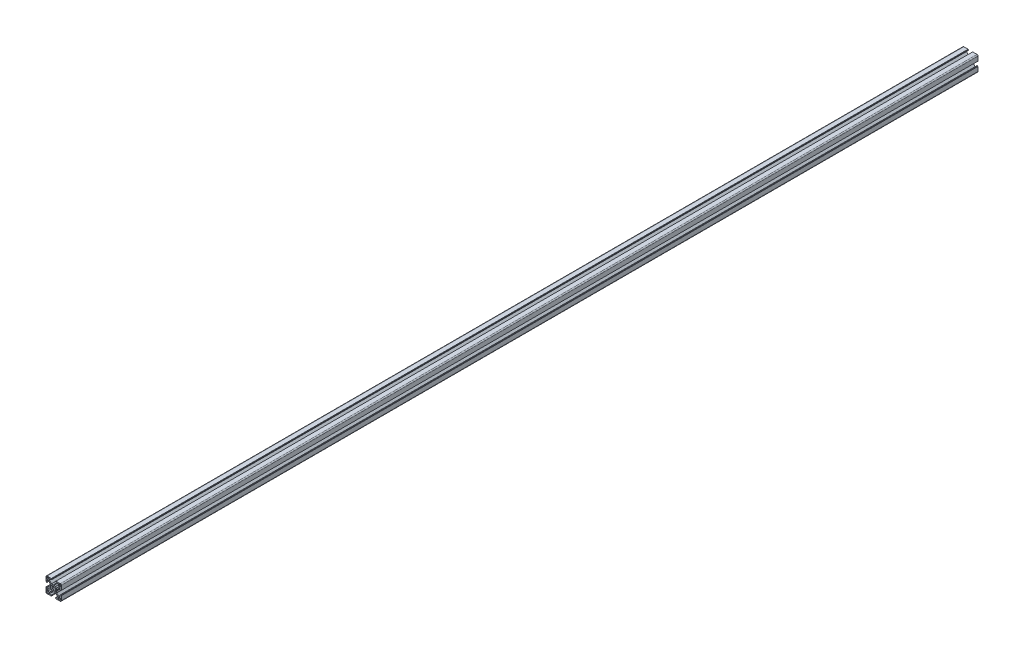
SolidWorks part; units mm, degrees
ref_plane "Front Plane" through (0, 0, 0) normal (0, 0, 1) x (1, 0, 0)
ref_plane "Top Plane" through (0, 0, 0) normal (0, 1, 0) x (1, 0, 0)
ref_plane "Right Plane" through (0, 0, 0) normal (1, 0, 0) x (0, 0, -1)
sketch "Sketch1" plane through (0, 0, 0) normal (0, 0, 1) x (1, 0, 0)
  line L0 (-15, 0) -> (15, 0) construction
  line L1 (0, -15) -> (0, 15) construction
  line L2 (-4.5, 15) -> (4.5, 15) construction
  line L3 (-4, -15) -> (4, -15) construction
  line L4 (-4.5, 15) -> (-4.5, 14.5)
  line L5 (-4.5, 14.5) -> (-4, 14.5)
  line L6 (-4, 14.5) -> (-4, 13.29)
  line L7 (-4.5, 12.79) -> (-7.7675, 12.79)
  line L8 (-8.2675, 12.29) -> (-8.2675, 10.2707)
  line L9 (-8.1211, 9.9171) -> (-4.3504, 6.1464)
  line L10 (-3.9968, 6) -> (0, 6)
  line L11 (0, 0) -> (-15, 15) construction
  line L12 (-4.5, 15) -> (-12.968, 15)
  line L14 (-12.705, 9.5135) -> (-10.5135, 9.5135)
  line L15 (-13.705, 10.5135) -> (-13.705, 12.705)
  line L16 (-12.705, 13.705) -> (-10.5135, 13.705)
  line L17 (-9.5135, 10.5135) -> (-9.5135, 12.705)
  line L18 (-13.705, 9.5135) -> (-9.5135, 13.705) construction
  line L19 (-13.705, 13.705) -> (-9.5135, 9.5135) construction
  line L20 (-3.1568, 4.5038) -> (-1.5303, 3.1477) construction
  line L21 (-4.5038, 3.1568) -> (-3.1477, 1.5303) construction
  line L22 (-6, 3.9968) -> (-6, 0)
  line L23 (-9.9171, 8.1211) -> (-6.1464, 4.3504)
  line L24 (-15, 4.5) -> (-15, 12.968)
  line L25 (-12.29, 8.2675) -> (-10.2707, 8.2675)
  line L26 (-12.79, 4.5) -> (-12.79, 7.7675)
  line L27 (-14.5, 4) -> (-13.29, 4)
  line L28 (-14.5, 4.5) -> (-14.5, 4)
  line L29 (-15, 4.5) -> (-14.5, 4.5)
  circle A0 centre (0, 0) radius 3.5
  arc A1 (-12.968, 15) -> (-15, 12.968) centre (-12.968, 12.968) ccw
  circle A2 centre (0, 0) radius 5.5 construction
  arc A3 (-10.5135, 9.5135) -> (-9.5135, 10.5135) centre (-10.5135, 10.5135) ccw
  arc A4 (-13.705, 12.705) -> (-12.705, 13.705) centre (-12.705, 12.705) cw
  arc A5 (-10.5135, 13.705) -> (-9.5135, 12.705) centre (-10.5135, 12.705) cw
  arc A6 (-12.705, 9.5135) -> (-13.705, 10.5135) centre (-12.705, 10.5135) cw
  arc A7 (-12.79, 4.5) -> (-13.29, 4) centre (-13.29, 4.5) cw
  arc A8 (-12.29, 8.2675) -> (-12.79, 7.7675) centre (-12.29, 7.7675) ccw
  arc A9 (-9.9171, 8.1211) -> (-10.2707, 8.2675) centre (-10.2707, 7.7675) ccw
  arc A10 (-6, 3.9968) -> (-6.1464, 4.3504) centre (-6.5, 3.9968) ccw
  arc A11 (-4.3504, 6.1464) -> (-3.9968, 6) centre (-3.9968, 6.5) ccw
  arc A12 (-4, 13.29) -> (-4.5, 12.79) centre (-4.5, 13.29) cw
  arc A13 (-7.7675, 12.79) -> (-8.2675, 12.29) centre (-7.7675, 12.29) ccw
  arc A14 (-8.2675, 10.2707) -> (-8.1211, 9.9171) centre (-7.7675, 10.2707) ccw
  point P4 (0, 0)
  point P8 (0, 0)
  point P13 (0, 15)
  point P15 (0, -15)
  point P16 (0, 6)
  point P23 (-11.6092, 11.6093)
  point P26 (0, 6)
  point P62 (-12.79, 4)
  point P65 (-12.79, 8.2675)
  point P68 (-10.0636, 8.2675)
  point P71 (-6, 4.2039)
  point P74 (-4.2039, 6)
  point P77 (-4, 12.79)
  point P80 (-8.2675, 12.79)
  point P83 (-8.2675, 10.0636)
  dimension "Center Hole Diameter" = 7
  dimension "D11" = 2.032
  dimension "D9" = 11
  dimension "D13" = 1
  dimension "D14" = 0.5
  dimension "Rail Height" = 30
  dimension "Rail Width" = 30
  dimension "T-Slot Width" = 8
  dimension "T-Slot Depth" = 9
  dimension "D1" = 9
  dimension "D2" = 45
  dimension "D3" = 8
  dimension "D4" = 2.21
  dimension "D5" = 16.535
  dimension "D7" = 2.54
  dimension "D6" = 1.295
  dimension "D8" = 1.246
  dimension "D10" = 10.36
  dimension "D12" = 1.905
sketch "Sketch2" plane through (0, 0, 0) normal (1, 0, 0) x (0, 0, -1)
  line L0 (-76.2, 0) -> (76.2, 0) construction
  line L2 (0, -15) -> (0, 15) construction
  line L3 (0, -15) -> (0, 15) construction
  line L4 (-76.2, -15) -> (-76.2, 15) construction
  line L5 (76.2, -15) -> (76.2, 15) construction
  point P0 (-38.7, 0)
  point P3 (0, 0)
  point P4 (38.7, 0)
  point P12 (-76.2, 0)
  point P14 (76.2, 0)
  dimension "Length" = 152.4
  dimension "D1" = 37.5
sketch "Sketch3" plane through (0, 0, 0) normal (0, 0, 1) x (1, 0, 0)
  line L0 (-4.5038, 3.1568) -> (-3.1477, 1.5303)
  line L1 (0, 3.5) -> (0, 5.5)
  line L2 (-5.5, 0) -> (-3.5, 0)
  line L7 (-6, 3.9968) -> (-6, 0) construction
  line L31 (-9.9171, 8.1211) -> (-6.1464, 4.3504) construction
  line L117 (-12.29, 8.2675) -> (-10.2707, 8.2675) construction
  line L118 (-12.79, 4.5) -> (-12.79, 7.7675) construction
  line L157 (-12.705, 9.5135) -> (-10.5135, 9.5135)
  line L158 (-9.5135, 10.5135) -> (-9.5135, 12.705)
  line L163 (-10.5135, 13.705) -> (-12.705, 13.705)
  line L164 (-13.705, 12.705) -> (-13.705, 10.5135)
  line L165 (-12.705, 9.5135) -> (-10.5135, 9.5135)
  line L166 (-9.5135, 10.5135) -> (-9.5135, 12.705)
  line L167 (-10.5135, 13.705) -> (-12.705, 13.705)
  line L168 (-13.705, 12.705) -> (-13.705, 10.5135)
  line L169 (-14.5, 4) -> (-13.29, 4) construction
  line L170 (-14.5, 4.5) -> (-14.5, 4) construction
  line L171 (-15, 4.5) -> (-14.5, 4.5) construction
  line L172 (-15, 4.5) -> (-15, 12.968) construction
  line L173 (-4.5, 15) -> (-12.968, 15) construction
  line L174 (-4.5, 15) -> (-4.5, 14.5) construction
  line L175 (-4.5, 14.5) -> (-4, 14.5) construction
  line L176 (-4, 14.5) -> (-4, 13.29) construction
  line L177 (-4.5, 12.79) -> (-7.7675, 12.79) construction
  line L178 (-8.2675, 12.29) -> (-8.2675, 10.2707) construction
  line L179 (-8.1211, 9.9171) -> (-4.3504, 6.1464) construction
  line L180 (-3.9968, 6) -> (0, 6) construction
  line L181 (-6, 3.9968) -> (-6, 0.866)
  line L182 (-9.9171, 8.1211) -> (-6.1464, 4.3504)
  line L183 (-12.29, 8.2675) -> (-10.2707, 8.2675)
  line L184 (-12.79, 4.5) -> (-12.79, 7.7675)
  line L185 (-14.5, 4) -> (-13.29, 4)
  line L186 (-14.5, 4.5) -> (-14.5, 4)
  line L187 (-15, 4.5) -> (-14.5, 4.5)
  line L188 (-15, 4.5) -> (-15, 12.968)
  line L189 (-4.5, 15) -> (-12.968, 15)
  line L190 (-4.5, 15) -> (-4.5, 14.5)
  line L191 (-4.5, 14.5) -> (-4, 14.5)
  line L192 (-4, 14.5) -> (-4, 13.29)
  line L193 (-4.5, 12.79) -> (-7.7675, 12.79)
  line L194 (-8.2675, 12.29) -> (-8.2675, 10.2707)
  line L195 (-8.1211, 9.9171) -> (-4.3504, 6.1464)
  line L196 (-3.9968, 6) -> (-0.866, 6)
  line L197 (-0.866, 6) -> (0, 5.5)
  line L198 (0, -15) -> (0, 15) construction
  line L199 (0, 0) -> (-15, 15) construction
  line L200 (0, 0) -> (-15, 15) construction
  line L201 (-3.1568, 4.5038) -> (-1.5303, 3.1477) construction
  line L202 (-3.1568, 4.5038) -> (-1.5303, 3.1477)
  line L203 (-6, 0.866) -> (-5.5, 0)
  line L204 (-15, 0) -> (15, 0) construction
  line L205 (-15, 0) -> (15, 0) construction
  line L206 (0, -15) -> (0, 15) construction
  arc A0 (-3.5, 0) -> (-3.1477, 1.5303) centre (0, 0) cw
  arc A10 (-6, 3.9968) -> (-6.1464, 4.3504) centre (-6.5, 3.9968) ccw construction
  circle A16 centre (0, 0) radius 3.5
  arc A18 (0, 3.5) -> (-1.5303, 3.1477) centre (0, 0) ccw
  arc A20 (-9.9171, 8.1211) -> (-10.2707, 8.2675) centre (-10.2707, 7.7675) ccw construction
  arc A22 (-12.29, 8.2675) -> (-12.79, 7.7675) centre (-12.29, 7.7675) ccw construction
  arc A28 (-13.29, 4) -> (-12.79, 4.5) centre (-13.29, 4.5) ccw construction
  arc A29 (-10.5135, 9.5135) -> (-9.5135, 10.5135) centre (-10.5135, 10.5135) ccw
  arc A30 (-9.5135, 12.705) -> (-10.5135, 13.705) centre (-10.5135, 12.705) ccw
  arc A31 (-12.705, 13.705) -> (-13.705, 12.705) centre (-12.705, 12.705) ccw
  arc A32 (-13.705, 10.5135) -> (-12.705, 9.5135) centre (-12.705, 10.5135) ccw
  arc A33 (-10.5135, 9.5135) -> (-9.5135, 10.5135) centre (-10.5135, 10.5135) ccw
  arc A34 (-9.5135, 12.705) -> (-10.5135, 13.705) centre (-10.5135, 12.705) ccw
  arc A35 (-12.705, 13.705) -> (-13.705, 12.705) centre (-12.705, 12.705) ccw
  arc A36 (-13.705, 10.5135) -> (-12.705, 9.5135) centre (-12.705, 10.5135) ccw
  arc A37 (-12.968, 15) -> (-15, 12.968) centre (-12.968, 12.968) ccw construction
  arc A38 (-4.5, 12.79) -> (-4, 13.29) centre (-4.5, 13.29) ccw construction
  arc A39 (-7.7675, 12.79) -> (-8.2675, 12.29) centre (-7.7675, 12.29) ccw construction
  arc A40 (-8.2675, 10.2707) -> (-8.1211, 9.9171) centre (-7.7675, 10.2707) ccw construction
  arc A41 (-4.3504, 6.1464) -> (-3.9968, 6) centre (-3.9968, 6.5) ccw construction
  arc A42 (-6, 3.9968) -> (-6.1464, 4.3504) centre (-6.5, 3.9968) ccw
  arc A43 (-9.9171, 8.1211) -> (-10.2707, 8.2675) centre (-10.2707, 7.7675) ccw
  arc A44 (-12.29, 8.2675) -> (-12.79, 7.7675) centre (-12.29, 7.7675) ccw
  arc A45 (-13.29, 4) -> (-12.79, 4.5) centre (-13.29, 4.5) ccw
  arc A46 (-12.968, 15) -> (-15, 12.968) centre (-12.968, 12.968) ccw
  arc A47 (-4.5, 12.79) -> (-4, 13.29) centre (-4.5, 13.29) ccw
  arc A48 (-7.7675, 12.79) -> (-8.2675, 12.29) centre (-7.7675, 12.29) ccw
  arc A49 (-8.2675, 10.2707) -> (-8.1211, 9.9171) centre (-7.7675, 10.2707) ccw
  arc A50 (-4.3504, 6.1464) -> (-3.9968, 6) centre (-3.9968, 6.5) ccw
  circle A51 centre (0, 0) radius 5.5 construction
  arc A52 (-3.1568, 4.5038) -> (-4.5038, 3.1568) centre (0, 0) ccw
  dimension "D3" = 60
  dimension "D4" = 60
  dimension "D1" = 0
  dimension "D2" = 0
extrude "Boss-Extrude1" add sketch "Sketch3" along normal mid plane 1800
pattern_circular "CirPattern1" count 4 over 360 about axis through (0, 0, 76.2) along (0, 0, -1) of "Boss-Extrude1"
ref_plane "Contact Plane1" through (15, 0, 0) normal (1, 0, 0) x (0, 0, -1)
ref_plane "Contact Plane2" through (0, -15, 0) normal (0, 1, 0) x (1, 0, 0)
ref_plane "Contact Plane3" through (-15, 0, 0) normal (1, 0, 0) x (0, 0, -1)
ref_plane "Contact Plane4" through (0, 15, 0) normal (0, 1, 0) x (1, 0, 0)
equation "\"D1@Sketch2\" = \"Rail Height@Sketch1\" * 1.25"
equation "\"D1@Sketch1\"=\"T-Slot Width@Sketch1\"+1mm"
equation "\"D3@Sketch1\"=\"T-Slot Width@Sketch1\""
equation "\"D1@Boss-Extrude1\"=\"length\""
equation "\"length\"= 1800"
